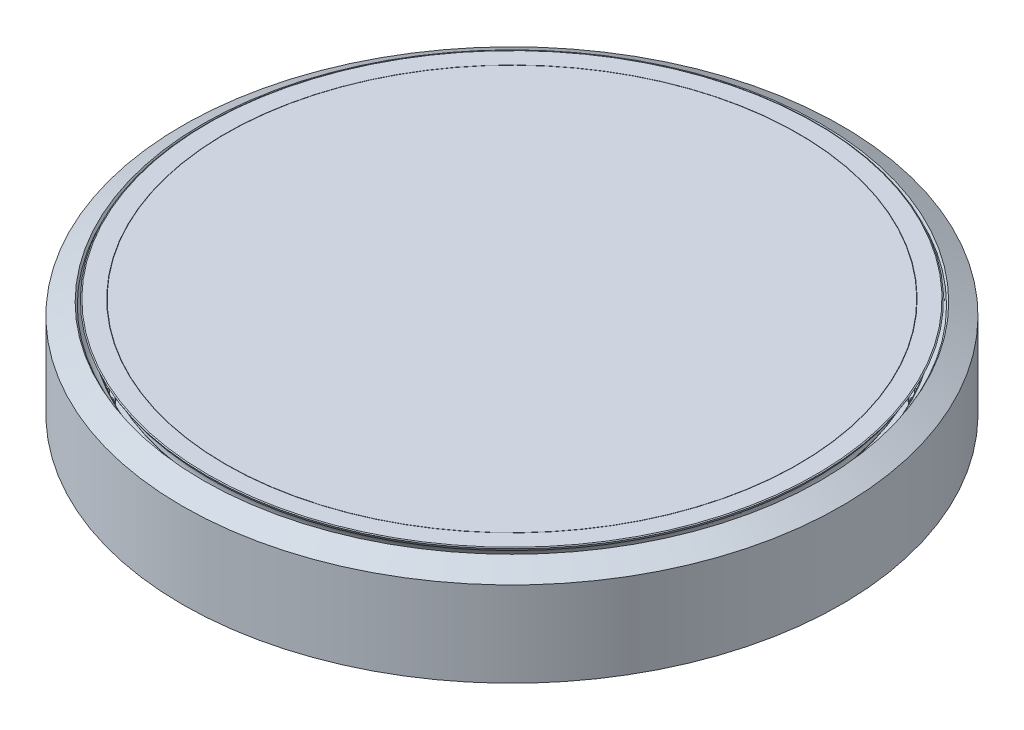
SolidWorks part; units mm, degrees
ref_plane "Front Plane" through (0, 0, 0) normal (0, 0, 1) x (1, 0, 0)
ref_plane "Top Plane" through (0, 0, 0) normal (0, 1, 0) x (1, 0, 0)
ref_plane "Right Plane" through (0, 0, 0) normal (1, 0, 0) x (0, 0, -1)
ref_axis "Cerberus" through (0, -55, 0) along (0, 1, 0)
sketch "Sketch1" plane through (0, 0, 0) normal (0, 0, 1) x (1, 0, 0)
  line L0 (0, 37.1533) -> (0, -37.1533) construction
  line L1 (0, 0) -> (-40.6181, 0) construction
  line L2 (-106.6534, 18.3868) -> (-103.3456, 12.6575) construction
  line L3 (-107.899, 19.0442) -> (-103.399, 11.25)
  line L4 (-106.6, 19.7942) -> (-102.1, 12)
  line L5 (-107.899, 19.0442) -> (-106.6, 19.7942) construction
  line L6 (-107.8946, 13.8507) -> (-102.1045, 17.1936) construction
  line L7 (-107.3662, 18.1213) -> (-106.0672, 18.8713) construction
  line L8 (-103.399, 11.25) -> (-105.1311, 10.25)
  line L9 (-105.1311, 10.25) -> (-105.1311, 0)
  line L10 (-107.899, 19.0442) -> (-115.1311, 14.8688)
  line L11 (-115.1311, 14.8688) -> (-115.1311, 0)
  line L12 (-106.6, 19.7942) -> (-106.2436, 20)
  line L13 (-106.2436, 20) -> (-100.1, 20)
  line L14 (-100.1, 20) -> (-100.1, 15)
  line L15 (-100.1, 15) -> (-98.1, 15)
  line L16 (-98.1, 15) -> (-98.1, 12)
  line L17 (-98.1, 12) -> (-102.1, 12)
  line L18 (-107.3662, 18.1213) -> (-107.3662, 20.0454) construction
  line L19 (-107.3662, 18.1213) -> (-107.1246, 19.4913) construction
  line L20 (-100, 20) -> (-100, 15)
  line L21 (-100, 15) -> (0, 15)
  line L22 (-100, 20) -> (0, 20)
  line L23 (-115.1311, 0) -> (-105.1311, 0)
  line L24 (0, 20) -> (0, 15)
  arc A0 (-107.3662, 18.1213) -> (-103.9319, 12.1729) centre (-102.1045, 17.1936) ccw
  arc A1 (-106.0672, 18.8713) -> (-102.6328, 12.9229) centre (-107.8946, 13.8507) cw
  circle A2 centre (-104.9995, 15.5221) radius 2 construction
  point P28 (-107.2495, 19.4192)
  point P30 (-104.9995, 15.5221)
  point P32 (-105.649, 15.1471)
  dimension "D8" = 4
  dimension "D1" = 60
  dimension "D2" = 1.5
  dimension "D3" = 10
  dimension "D4" = 5
  dimension "D5" = 9
  dimension "D6" = 2
  dimension "D7" = 3
  dimension "D9" = 0.1
  dimension "D10" = 200
  dimension "D11" = 10
  dimension "D12" = 2
  dimension "D13" = 40
  dimension "D14" = 2
revolve "Revolve1" add sketch "Sketch1" angle 360 about L0 region at (-110.0853, 8.328, 0) region at (-101.6249, 16.2478, 0)
revolve "Revolve2" add sketch "Sketch1<6>" angle 360 about L0 region at (-50, 17.5, 0)
sketch "Sketch1<6>" plane through (0, 0, 0) normal (0, 0, 1) x (1, 0, 0) same geometry as "Sketch1"
mirror "Mirror3" about plane through (0, 0, 0) normal (0, 1, 0) of bodies 101 103 102
combine bodies "Combine2" operation type add bodies to combine 101 108
sketch "Sketch2" plane through (0, 0, 0) normal (0, 1, 0) x (1, 0, 0)
  line L0 (0, 0) -> (0, 105.1311) construction
  line L1 (-2.314, 105.1056) -> (-1.1228, 100.8281)
  line L2 (-1.1228, 100.8281) -> (1.1228, 100.8281)
  line L3 (1.1228, 100.8281) -> (2.314, 105.1056)
  circle A0 centre (0, 0) radius 105.1311 construction
  arc A1 (-2.314, 105.1056) -> (2.314, 105.1056) centre (0, 0) cw
  point P8 (1.1228, 100.8281)
  point P11 (0, 0)
  point P12 (2.314, 105.1311)
  point P13 (0, 0)
extrude "Boss-Extrude1" add sketch "Sketch2" along normal mid plane 10
pattern_circular "CirPattern1" count 100 over 360 about axis through (0, -55, 0) along (0, 1, 0) of "Boss-Extrude1"
